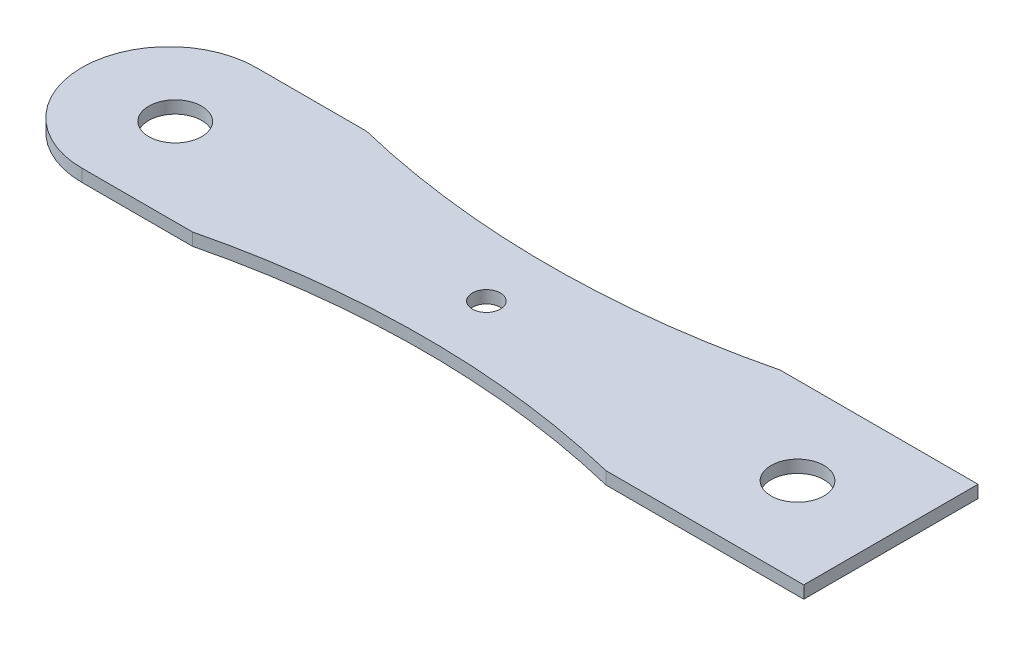
SolidWorks part; units mm, degrees
ref_plane "前视" through (0, 0, 0) normal (0, 0, 1) x (1, 0, 0)
ref_plane "上视" through (0, 0, 0) normal (0, 1, 0) x (1, 0, 0)
ref_plane "右视" through (0, 0, 0) normal (1, 0, 0) x (0, 0, -1)
sketch "草图1" plane through (0, 0, 0) normal (0, 1, 0) x (1, 0, 0)
  line L1 (-65, 14) -> (65, 14)
  line L2 (-65, 14) -> (-65, -14)
  line L3 (-65, -14) -> (65, -14)
  line L4 (65, 14) -> (65, -14)
  line L5 (-65, 14) -> (65, -14) construction
  line L6 (-65, -14) -> (65, 14) construction
  point P0 (0, 0)
  dimension "D1" = 130
  dimension "D2" = 28
extrude "凸台-拉伸1" add sketch "草图1" along normal blind 2 contours L2 | L2 | L3 L1 | L4 | L4 region at (0, 0, 0)
sketch "草图2" plane through (0, 2, 0) normal (0, 1, 0) x (1, 0, 0)
  circle A0 centre (-50, 0) radius 4.25
  circle A1 centre (50, 0) radius 4.25
  circle A2 centre (0, 0) radius 2.25
  dimension "D1" = 8.5
  dimension "D2" = 8.5
  dimension "D5" = 4.5
  dimension "D3" = 100
  dimension "D4" = 50
extrude "切除-拉伸1" cut sketch "草图2" against normal up to next
fillet "圆角1" 2 edges at (-65, 1, 14) (-65, 1, -14) type full round first side face at (0, 1, 14) second side face at (0, 1, -14) middle face at (-65, 1, 0)
sketch "草图3" plane through (0, 2, 0) normal (0, 1, 0) x (1, 0, 0)
  circle A0 centre (-68.5, 0) radius 2.25
  circle A1 centre (-31.5, 0) radius 2.25
  circle A2 centre (31.5, 0) radius 2.25
  circle A3 centre (68.5, 0) radius 2.25
  circle A4 centre (-50, 0) radius 4.25 construction
  circle A5 centre (50, 0) radius 4.25 construction
  dimension "D2" = 18.5
  dimension "D3" = 4.5
  dimension "D4" = 4.5
  dimension "D6" = 18.5
  dimension "D7" = 4.5
  dimension "D8" = 4.5
  dimension "D1" = 37
  dimension "D5" = 37
extrude "切除-拉伸2" [suppressed] cut sketch "草图3" against normal up to next
sketch "草图4" plane through (0, 2, 0) normal (0, 1, 0) x (1, 0, 0)
  circle A0 centre (0, 150) radius 140
  dimension "D2" = 280
  dimension "D1" = 150
extrude "切除-拉伸3" cut sketch "草图4" against normal up to next
mirror "镜向1" about plane through (0, 0, 0) normal (0, 0, 1) of "切除-拉伸3"
